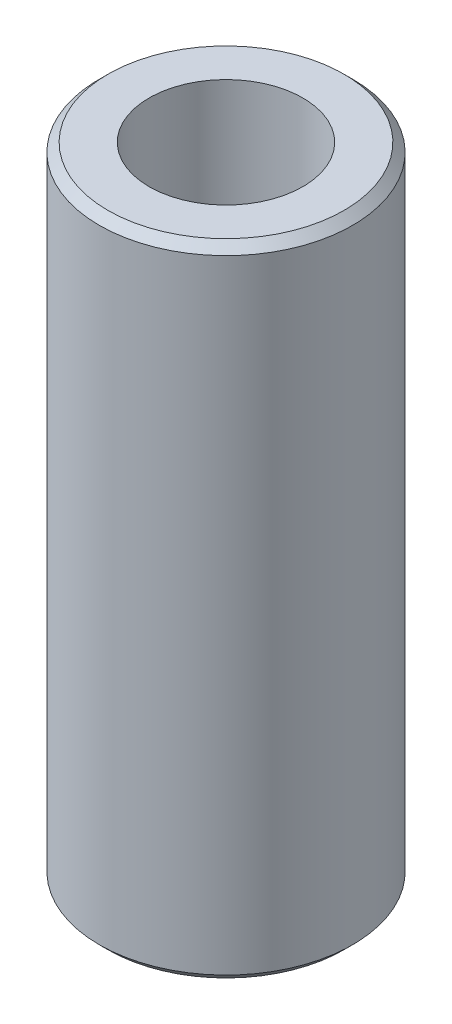
SolidWorks part; units mm, degrees
ref_plane "Front Plane" through (0, 0, 0) normal (0, 0, 1) x (1, 0, 0)
ref_plane "Top Plane" through (0, 0, 0) normal (0, 1, 0) x (1, 0, 0)
ref_plane "Right Plane" through (0, 0, 0) normal (1, 0, 0) x (0, 0, -1)
sketch "Sketch1" plane through (0, 0, 0) normal (0, 1, 0) x (1, 0, 0)
  circle A0 centre (0, 0) radius 57.5
  dimension "SHAFT_OD" = 115
extrude "Boss-Extrude1" add sketch "Sketch1" along normal blind 290.6826
sketch "Sketch2" plane through (0, 0, 0) normal (0, 1, 0) x (1, 0, 0)
  circle A0 centre (0, 0) radius 34.9107
  dimension "BORE_D" = 69.8214
extrude "Cut-Extrude1" cut sketch "Sketch2" along normal through all
chamfer "Chamfer1" distance 3.913 angle 45 2 edges at (0, 290.6826, 57.5) (0, 0, 57.5)
